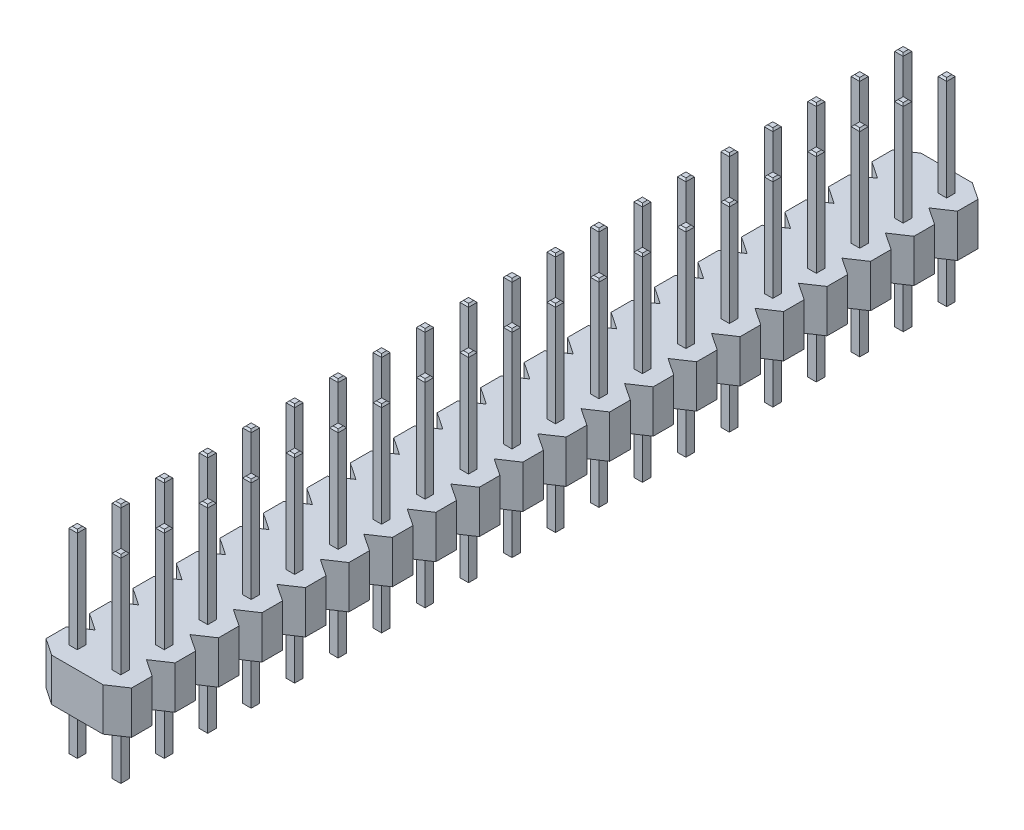
SolidWorks part; units mm, degrees
ref_plane "Front" through (0, 0, 0) normal (0, 0, 1) x (1, 0, 0)
ref_plane "Top" through (0, 0, 0) normal (0, 1, 0) x (1, 0, 0)
ref_plane "Right" through (0, 0, 0) normal (1, 0, 0) x (0, 0, -1)
ref_plane "Plan1" through (0, 2.5, 0) normal (0, 1, 0) x (1, 0, 0)
sketch "Esquisse1" plane through (0, 2.5, 0) normal (0, 1, 0) x (1, 0, 0)
  line L0 (2.5, -23.46) -> (2.5, 26)
  line L1 (2.5, 26) -> (1.5, 26.67)
  line L2 (1.5, 26.67) -> (-1.5, 26.67)
  line L3 (-1.5, 26.67) -> (-2.5, 26)
  line L4 (-2.5, 26) -> (-2.5, -23.46)
  line L5 (-2.5, -23.46) -> (-1.5, -24.13)
  line L6 (-1.5, -24.13) -> (1.5, -24.13)
  line L7 (1.5, -24.13) -> (2.5, -23.46)
extrude "Boss.-Extru.1" add sketch "Esquisse1" against normal blind 2.5
sketch "Esquisse2" plane through (0, 0, 0) normal (0, -1, 0) x (1, 0, 0)
  line L0 (-2.5, 7.02) -> (-2.5, 5.68)
  line L1 (-2.5, 5.68) -> (-1.5, 6.35)
  line L2 (-1.5, 6.35) -> (-2.5, 7.02)
extrude "Enlèv. mat.-Extru.1" cut sketch "Esquisse2" against normal through all
sketch "Esquisse3" plane through (0, 0, 0) normal (0, -1, 0) x (1, 0, 0)
  line L0 (-2.5, 9.56) -> (-2.5, 8.22)
  line L1 (-2.5, 8.22) -> (-1.5, 8.89)
  line L2 (-1.5, 8.89) -> (-2.5, 9.56)
extrude "Enlèv. mat.-Extru.2" cut sketch "Esquisse3" against normal through all
sketch "Esquisse4" plane through (0, 0, 0) normal (0, -1, 0) x (1, 0, 0)
  line L0 (-2.5, 12.1) -> (-2.5, 10.76)
  line L1 (-2.5, 10.76) -> (-1.5, 11.43)
  line L2 (-1.5, 11.43) -> (-2.5, 12.1)
extrude "Enlèv. mat.-Extru.3" cut sketch "Esquisse4" against normal through all
sketch "Esquisse5" plane through (0, 0, 0) normal (0, -1, 0) x (1, 0, 0)
  line L0 (-2.5, 14.64) -> (-2.5, 13.3)
  line L1 (-2.5, 13.3) -> (-1.5, 13.97)
  line L2 (-1.5, 13.97) -> (-2.5, 14.64)
extrude "Enlèv. mat.-Extru.4" cut sketch "Esquisse5" against normal through all
sketch "Esquisse6" plane through (0, 0, 0) normal (0, -1, 0) x (1, 0, 0)
  line L0 (-2.5, 17.18) -> (-2.5, 15.84)
  line L1 (-2.5, 15.84) -> (-1.5, 16.51)
  line L2 (-1.5, 16.51) -> (-2.5, 17.18)
extrude "Enlèv. mat.-Extru.5" cut sketch "Esquisse6" against normal through all
sketch "Esquisse7" plane through (0, 0, 0) normal (0, -1, 0) x (1, 0, 0)
  line L0 (-2.5, 19.72) -> (-2.5, 18.38)
  line L1 (-2.5, 18.38) -> (-1.5, 19.05)
  line L2 (-1.5, 19.05) -> (-2.5, 19.72)
extrude "Enlèv. mat.-Extru.6" cut sketch "Esquisse7" against normal through all
sketch "Esquisse8" plane through (0, 0, 0) normal (0, -1, 0) x (1, 0, 0)
  line L0 (-2.5, 22.26) -> (-2.5, 20.92)
  line L1 (-2.5, 20.92) -> (-1.5, 21.59)
  line L2 (-1.5, 21.59) -> (-2.5, 22.26)
extrude "Enlèv. mat.-Extru.7" cut sketch "Esquisse8" against normal through all
sketch "Esquisse9" plane through (0, 0, 0) normal (0, -1, 0) x (1, 0, 0)
  line L0 (2.5, 20.92) -> (2.5, 22.26)
  line L1 (2.5, 22.26) -> (1.5, 21.59)
  line L2 (1.5, 21.59) -> (2.5, 20.92)
extrude "Enlèv. mat.-Extru.8" cut sketch "Esquisse9" against normal through all
sketch "Esquisse10" plane through (0, 0, 0) normal (0, -1, 0) x (1, 0, 0)
  line L0 (2.5, 18.38) -> (2.5, 19.72)
  line L1 (2.5, 19.72) -> (1.5, 19.05)
  line L2 (1.5, 19.05) -> (2.5, 18.38)
extrude "Enlèv. mat.-Extru.9" cut sketch "Esquisse10" against normal through all
sketch "Esquisse11" plane through (0, 0, 0) normal (0, -1, 0) x (1, 0, 0)
  line L0 (2.5, 15.84) -> (2.5, 17.18)
  line L1 (2.5, 17.18) -> (1.5, 16.51)
  line L2 (1.5, 16.51) -> (2.5, 15.84)
extrude "Enlèv. mat.-Extru.10" cut sketch "Esquisse11" against normal through all
sketch "Esquisse12" plane through (0, 0, 0) normal (0, -1, 0) x (1, 0, 0)
  line L0 (2.5, 13.3) -> (2.5, 14.64)
  line L1 (2.5, 14.64) -> (1.5, 13.97)
  line L2 (1.5, 13.97) -> (2.5, 13.3)
extrude "Enlèv. mat.-Extru.11" cut sketch "Esquisse12" against normal through all
sketch "Esquisse13" plane through (0, 0, 0) normal (0, -1, 0) x (1, 0, 0)
  line L0 (2.5, 10.76) -> (2.5, 12.1)
  line L1 (2.5, 12.1) -> (1.5, 11.43)
  line L2 (1.5, 11.43) -> (2.5, 10.76)
extrude "Enlèv. mat.-Extru.12" cut sketch "Esquisse13" against normal through all
sketch "Esquisse14" plane through (0, 0, 0) normal (0, -1, 0) x (1, 0, 0)
  line L0 (2.5, 8.22) -> (2.5, 9.56)
  line L1 (2.5, 9.56) -> (1.5, 8.89)
  line L2 (1.5, 8.89) -> (2.5, 8.22)
extrude "Enlèv. mat.-Extru.13" cut sketch "Esquisse14" against normal through all
sketch "Esquisse15" plane through (0, 0, 0) normal (0, -1, 0) x (1, 0, 0)
  line L0 (2.5, 5.68) -> (2.5, 7.02)
  line L1 (2.5, 7.02) -> (1.5, 6.35)
  line L2 (1.5, 6.35) -> (2.5, 5.68)
extrude "Enlèv. mat.-Extru.14" cut sketch "Esquisse15" against normal through all
sketch "Esquisse16" plane through (0, 0, 0) normal (0, -1, 0) x (1, 0, 0)
  line L0 (2.5, 3.14) -> (2.5, 4.48)
  line L1 (2.5, 4.48) -> (1.5, 3.81)
  line L2 (1.5, 3.81) -> (2.5, 3.14)
extrude "Enlèv. mat.-Extru.15" cut sketch "Esquisse16" against normal through all
sketch "Esquisse17" plane through (0, 0, 0) normal (0, -1, 0) x (1, 0, 0)
  line L0 (2.5, 0.6) -> (2.5, 1.94)
  line L1 (2.5, 1.94) -> (1.5, 1.27)
  line L2 (1.5, 1.27) -> (2.5, 0.6)
extrude "Enlèv. mat.-Extru.16" cut sketch "Esquisse17" against normal through all
sketch "Esquisse18" plane through (0, 0, 0) normal (0, -1, 0) x (1, 0, 0)
  line L0 (2.5, -1.94) -> (2.5, -0.6)
  line L1 (2.5, -0.6) -> (1.5, -1.27)
  line L2 (1.5, -1.27) -> (2.5, -1.94)
extrude "Enlèv. mat.-Extru.17" cut sketch "Esquisse18" against normal through all
sketch "Esquisse19" plane through (0, 0, 0) normal (0, -1, 0) x (1, 0, 0)
  line L0 (2.5, -4.48) -> (2.5, -3.14)
  line L1 (2.5, -3.14) -> (1.5, -3.81)
  line L2 (1.5, -3.81) -> (2.5, -4.48)
extrude "Enlèv. mat.-Extru.18" cut sketch "Esquisse19" against normal through all
sketch "Esquisse20" plane through (0, 0, 0) normal (0, -1, 0) x (1, 0, 0)
  line L0 (2.5, -7.02) -> (2.5, -5.68)
  line L1 (2.5, -5.68) -> (1.5, -6.35)
  line L2 (1.5, -6.35) -> (2.5, -7.02)
extrude "Enlèv. mat.-Extru.19" cut sketch "Esquisse20" against normal through all
sketch "Esquisse21" plane through (0, 0, 0) normal (0, -1, 0) x (1, 0, 0)
  line L0 (2.5, -9.56) -> (2.5, -8.22)
  line L1 (2.5, -8.22) -> (1.5, -8.89)
  line L2 (1.5, -8.89) -> (2.5, -9.56)
extrude "Enlèv. mat.-Extru.20" cut sketch "Esquisse21" against normal through all
sketch "Esquisse22" plane through (0, 0, 0) normal (0, -1, 0) x (1, 0, 0)
  line L0 (2.5, -12.1) -> (2.5, -10.76)
  line L1 (2.5, -10.76) -> (1.5, -11.43)
  line L2 (1.5, -11.43) -> (2.5, -12.1)
extrude "Enlèv. mat.-Extru.21" cut sketch "Esquisse22" against normal through all
sketch "Esquisse23" plane through (0, 0, 0) normal (0, -1, 0) x (1, 0, 0)
  line L0 (2.5, -14.64) -> (2.5, -13.3)
  line L1 (2.5, -13.3) -> (1.5, -13.97)
  line L2 (1.5, -13.97) -> (2.5, -14.64)
extrude "Enlèv. mat.-Extru.22" cut sketch "Esquisse23" against normal through all
sketch "Esquisse24" plane through (0, 0, 0) normal (0, -1, 0) x (1, 0, 0)
  line L0 (2.5, -17.18) -> (2.5, -15.84)
  line L1 (2.5, -15.84) -> (1.5, -16.51)
  line L2 (1.5, -16.51) -> (2.5, -17.18)
extrude "Enlèv. mat.-Extru.23" cut sketch "Esquisse24" against normal through all
sketch "Esquisse25" plane through (0, 0, 0) normal (0, -1, 0) x (1, 0, 0)
  line L0 (2.5, -19.72) -> (2.5, -18.38)
  line L1 (2.5, -18.38) -> (1.5, -19.05)
  line L2 (1.5, -19.05) -> (2.5, -19.72)
extrude "Enlèv. mat.-Extru.24" cut sketch "Esquisse25" against normal through all
sketch "Esquisse26" plane through (0, 0, 0) normal (0, -1, 0) x (1, 0, 0)
  line L0 (2.5, -22.26) -> (2.5, -20.92)
  line L1 (2.5, -20.92) -> (1.5, -21.59)
  line L2 (1.5, -21.59) -> (2.5, -22.26)
extrude "Enlèv. mat.-Extru.25" cut sketch "Esquisse26" against normal through all
sketch "Esquisse27" plane through (0, 0, 0) normal (0, -1, 0) x (1, 0, 0)
  line L0 (2.5, -24.8) -> (2.5, -23.46)
  line L1 (2.5, -23.46) -> (1.5, -24.13)
  line L2 (1.5, -24.13) -> (2.5, -24.8)
extrude "Enlèv. mat.-Extru.26" cut sketch "Esquisse27" against normal through all
sketch "Esquisse28" plane through (0, 0, 0) normal (0, -1, 0) x (1, 0, 0)
  line L0 (-2.5, -23.46) -> (-2.5, -24.8)
  line L1 (-2.5, -24.8) -> (-1.5, -24.13)
  line L2 (-1.5, -24.13) -> (-2.5, -23.46)
extrude "Enlèv. mat.-Extru.27" cut sketch "Esquisse28" against normal through all
sketch "Esquisse29" plane through (0, 0, 0) normal (0, -1, 0) x (1, 0, 0)
  line L0 (-2.5, -20.92) -> (-2.5, -22.26)
  line L1 (-2.5, -22.26) -> (-1.5, -21.59)
  line L2 (-1.5, -21.59) -> (-2.5, -20.92)
extrude "Enlèv. mat.-Extru.28" cut sketch "Esquisse29" against normal through all
sketch "Esquisse30" plane through (0, 0, 0) normal (0, -1, 0) x (1, 0, 0)
  line L0 (-2.5, -18.38) -> (-2.5, -19.72)
  line L1 (-2.5, -19.72) -> (-1.5, -19.05)
  line L2 (-1.5, -19.05) -> (-2.5, -18.38)
extrude "Enlèv. mat.-Extru.29" cut sketch "Esquisse30" against normal through all
sketch "Esquisse31" plane through (0, 0, 0) normal (0, -1, 0) x (1, 0, 0)
  line L0 (-2.5, -15.84) -> (-2.5, -17.18)
  line L1 (-2.5, -17.18) -> (-1.5, -16.51)
  line L2 (-1.5, -16.51) -> (-2.5, -15.84)
extrude "Enlèv. mat.-Extru.30" cut sketch "Esquisse31" against normal through all
sketch "Esquisse32" plane through (0, 0, 0) normal (0, -1, 0) x (1, 0, 0)
  line L0 (-2.5, -13.3) -> (-2.5, -14.64)
  line L1 (-2.5, -14.64) -> (-1.5, -13.97)
  line L2 (-1.5, -13.97) -> (-2.5, -13.3)
extrude "Enlèv. mat.-Extru.31" cut sketch "Esquisse32" against normal through all
sketch "Esquisse33" plane through (0, 0, 0) normal (0, -1, 0) x (1, 0, 0)
  line L0 (-2.5, -10.76) -> (-2.5, -12.1)
  line L1 (-2.5, -12.1) -> (-1.5, -11.43)
  line L2 (-1.5, -11.43) -> (-2.5, -10.76)
extrude "Enlèv. mat.-Extru.32" cut sketch "Esquisse33" against normal through all
sketch "Esquisse34" plane through (0, 0, 0) normal (0, -1, 0) x (1, 0, 0)
  line L0 (-2.5, -8.22) -> (-2.5, -9.56)
  line L1 (-2.5, -9.56) -> (-1.5, -8.89)
  line L2 (-1.5, -8.89) -> (-2.5, -8.22)
extrude "Enlèv. mat.-Extru.33" cut sketch "Esquisse34" against normal through all
sketch "Esquisse35" plane through (0, 0, 0) normal (0, -1, 0) x (1, 0, 0)
  line L0 (-2.5, -5.68) -> (-2.5, -7.02)
  line L1 (-2.5, -7.02) -> (-1.5, -6.35)
  line L2 (-1.5, -6.35) -> (-2.5, -5.68)
extrude "Enlèv. mat.-Extru.34" cut sketch "Esquisse35" against normal through all
sketch "Esquisse36" plane through (0, 0, 0) normal (0, -1, 0) x (1, 0, 0)
  line L0 (-2.5, -3.14) -> (-2.5, -4.48)
  line L1 (-2.5, -4.48) -> (-1.5, -3.81)
  line L2 (-1.5, -3.81) -> (-2.5, -3.14)
extrude "Enlèv. mat.-Extru.35" cut sketch "Esquisse36" against normal through all
sketch "Esquisse37" plane through (0, 0, 0) normal (0, -1, 0) x (1, 0, 0)
  line L0 (-2.5, -0.6) -> (-2.5, -1.94)
  line L1 (-2.5, -1.94) -> (-1.5, -1.27)
  line L2 (-1.5, -1.27) -> (-2.5, -0.6)
extrude "Enlèv. mat.-Extru.36" cut sketch "Esquisse37" against normal through all
sketch "Esquisse38" plane through (0, 0, 0) normal (0, -1, 0) x (1, 0, 0)
  line L0 (-2.5, 1.94) -> (-2.5, 0.6)
  line L1 (-2.5, 0.6) -> (-1.5, 1.27)
  line L2 (-1.5, 1.27) -> (-2.5, 1.94)
extrude "Enlèv. mat.-Extru.37" cut sketch "Esquisse38" against normal through all
sketch "Esquisse39" plane through (0, 0, 0) normal (0, -1, 0) x (1, 0, 0)
  line L0 (-2.5, 4.48) -> (-2.5, 3.14)
  line L1 (-2.5, 3.14) -> (-1.5, 3.81)
  line L2 (-1.5, 3.81) -> (-2.5, 4.48)
extrude "Enlèv. mat.-Extru.38" cut sketch "Esquisse39" against normal through all
sketch "Esquisse40" plane through (0, 2.5, 0) normal (0, 1, 0) x (-1, 0, 0)
  line L0 (1.02, -2.29) -> (1.52, -2.29)
  line L1 (1.52, -2.29) -> (1.52, -2.79)
  line L2 (1.52, -2.79) -> (1.02, -2.79)
  line L3 (1.02, -2.79) -> (1.02, -2.29)
extrude "Boss.-Extru.2" add sketch "Esquisse40" along normal blind 6
sketch "Esquisse41" plane through (0, 2.5, 0) normal (0, 1, 0) x (-1, 0, 0)
  line L0 (-1.52, -2.79) -> (-1.52, -2.29)
  line L1 (-1.52, -2.29) -> (-1.02, -2.29)
  line L2 (-1.02, -2.29) -> (-1.02, -2.79)
  line L3 (-1.02, -2.79) -> (-1.52, -2.79)
extrude "Boss.-Extru.3" add sketch "Esquisse41" along normal blind 6
sketch "Esquisse42" plane through (0, 2.5, 0) normal (0, 1, 0) x (-1, 0, 0)
  line L0 (-1.52, -5.33) -> (-1.52, -4.83)
  line L1 (-1.52, -4.83) -> (-1.02, -4.83)
  line L2 (-1.02, -4.83) -> (-1.02, -5.33)
  line L3 (-1.02, -5.33) -> (-1.52, -5.33)
extrude "Boss.-Extru.4" add sketch "Esquisse42" along normal blind 6
sketch "Esquisse43" plane through (0, 2.5, 0) normal (0, 1, 0) x (-1, 0, 0)
  line L0 (1.02, -5.33) -> (1.02, -4.83)
  line L1 (1.02, -4.83) -> (1.52, -4.83)
  line L2 (1.52, -4.83) -> (1.52, -5.33)
  line L3 (1.52, -5.33) -> (1.02, -5.33)
extrude "Boss.-Extru.5" add sketch "Esquisse43" along normal blind 6
sketch "Esquisse44" plane through (0, 2.5, 0) normal (0, 1, 0) x (-1, 0, 0)
  line L0 (-1.52, -7.87) -> (-1.52, -7.37)
  line L1 (-1.52, -7.37) -> (-1.02, -7.37)
  line L2 (-1.02, -7.37) -> (-1.02, -7.87)
  line L3 (-1.02, -7.87) -> (-1.52, -7.87)
extrude "Boss.-Extru.6" add sketch "Esquisse44" along normal blind 6
sketch "Esquisse45" plane through (0, 2.5, 0) normal (0, 1, 0) x (-1, 0, 0)
  line L0 (1.02, -7.87) -> (1.02, -7.37)
  line L1 (1.02, -7.37) -> (1.52, -7.37)
  line L2 (1.52, -7.37) -> (1.52, -7.87)
  line L3 (1.52, -7.87) -> (1.02, -7.87)
extrude "Boss.-Extru.7" add sketch "Esquisse45" along normal blind 6
sketch "Esquisse46" plane through (0, 2.5, 0) normal (0, 1, 0) x (-1, 0, 0)
  line L0 (-1.52, -10.41) -> (-1.52, -9.91)
  line L1 (-1.52, -9.91) -> (-1.02, -9.91)
  line L2 (-1.02, -9.91) -> (-1.02, -10.41)
  line L3 (-1.02, -10.41) -> (-1.52, -10.41)
extrude "Boss.-Extru.8" add sketch "Esquisse46" along normal blind 6
sketch "Esquisse47" plane through (0, 2.5, 0) normal (0, 1, 0) x (-1, 0, 0)
  line L0 (1.52, -9.91) -> (1.52, -10.41)
  line L1 (1.52, -10.41) -> (1.02, -10.41)
  line L2 (1.02, -10.41) -> (1.02, -9.91)
  line L3 (1.02, -9.91) -> (1.52, -9.91)
extrude "Boss.-Extru.9" add sketch "Esquisse47" along normal blind 6
sketch "Esquisse48" plane through (0, 2.5, 0) normal (0, 1, 0) x (-1, 0, 0)
  line L0 (-1.52, -12.95) -> (-1.52, -12.45)
  line L1 (-1.52, -12.45) -> (-1.02, -12.45)
  line L2 (-1.02, -12.45) -> (-1.02, -12.95)
  line L3 (-1.02, -12.95) -> (-1.52, -12.95)
extrude "Boss.-Extru.10" add sketch "Esquisse48" along normal blind 6
sketch "Esquisse49" plane through (0, 2.5, 0) normal (0, 1, 0) x (-1, 0, 0)
  line L0 (1.02, -12.95) -> (1.02, -12.45)
  line L1 (1.02, -12.45) -> (1.52, -12.45)
  line L2 (1.52, -12.45) -> (1.52, -12.95)
  line L3 (1.52, -12.95) -> (1.02, -12.95)
extrude "Boss.-Extru.11" add sketch "Esquisse49" along normal blind 6
sketch "Esquisse50" plane through (0, 2.5, 0) normal (0, 1, 0) x (-1, 0, 0)
  line L0 (-1.52, -15.49) -> (-1.52, -14.99)
  line L1 (-1.52, -14.99) -> (-1.02, -14.99)
  line L2 (-1.02, -14.99) -> (-1.02, -15.49)
  line L3 (-1.02, -15.49) -> (-1.52, -15.49)
extrude "Boss.-Extru.12" add sketch "Esquisse50" along normal blind 6
sketch "Esquisse51" plane through (0, 2.5, 0) normal (0, 1, 0) x (-1, 0, 0)
  line L0 (1.02, -15.49) -> (1.02, -14.99)
  line L1 (1.02, -14.99) -> (1.52, -14.99)
  line L2 (1.52, -14.99) -> (1.52, -15.49)
  line L3 (1.52, -15.49) -> (1.02, -15.49)
extrude "Boss.-Extru.13" add sketch "Esquisse51" along normal blind 6
sketch "Esquisse52" plane through (0, 2.5, 0) normal (0, 1, 0) x (-1, 0, 0)
  line L0 (-1.52, -18.03) -> (-1.52, -17.53)
  line L1 (-1.52, -17.53) -> (-1.02, -17.53)
  line L2 (-1.02, -17.53) -> (-1.02, -18.03)
  line L3 (-1.02, -18.03) -> (-1.52, -18.03)
extrude "Boss.-Extru.14" add sketch "Esquisse52" along normal blind 6
sketch "Esquisse53" plane through (0, 2.5, 0) normal (0, 1, 0) x (-1, 0, 0)
  line L0 (1.02, -18.03) -> (1.02, -17.53)
  line L1 (1.02, -17.53) -> (1.52, -17.53)
  line L2 (1.52, -17.53) -> (1.52, -18.03)
  line L3 (1.52, -18.03) -> (1.02, -18.03)
extrude "Boss.-Extru.15" add sketch "Esquisse53" along normal blind 6
sketch "Esquisse54" plane through (0, 2.5, 0) normal (0, 1, 0) x (-1, 0, 0)
  line L0 (-1.52, -20.57) -> (-1.52, -20.07)
  line L1 (-1.52, -20.07) -> (-1.02, -20.07)
  line L2 (-1.02, -20.07) -> (-1.02, -20.57)
  line L3 (-1.02, -20.57) -> (-1.52, -20.57)
extrude "Boss.-Extru.16" add sketch "Esquisse54" along normal blind 6
sketch "Esquisse55" plane through (0, 2.5, 0) normal (0, 1, 0) x (-1, 0, 0)
  line L0 (1.52, -20.07) -> (1.52, -20.57)
  line L1 (1.52, -20.57) -> (1.02, -20.57)
  line L2 (1.02, -20.57) -> (1.02, -20.07)
  line L3 (1.02, -20.07) -> (1.52, -20.07)
extrude "Boss.-Extru.17" add sketch "Esquisse55" along normal blind 6
sketch "Esquisse56" plane through (0, 2.5, 0) normal (0, 1, 0) x (-1, 0, 0)
  line L0 (-1.52, -23.11) -> (-1.52, -22.61)
  line L1 (-1.52, -22.61) -> (-1.02, -22.61)
  line L2 (-1.02, -22.61) -> (-1.02, -23.11)
  line L3 (-1.02, -23.11) -> (-1.52, -23.11)
extrude "Boss.-Extru.18" add sketch "Esquisse56" along normal blind 6
sketch "Esquisse57" plane through (0, 2.5, 0) normal (0, 1, 0) x (-1, 0, 0)
  line L0 (1.02, -23.11) -> (1.02, -22.61)
  line L1 (1.02, -22.61) -> (1.52, -22.61)
  line L2 (1.52, -22.61) -> (1.52, -23.11)
  line L3 (1.52, -23.11) -> (1.02, -23.11)
extrude "Boss.-Extru.19" add sketch "Esquisse57" along normal blind 6
sketch "Esquisse58" plane through (0, 2.5, 0) normal (0, 1, 0) x (-1, 0, 0)
  line L0 (-1.52, -25.65) -> (-1.52, -25.15)
  line L1 (-1.52, -25.15) -> (-1.02, -25.15)
  line L2 (-1.02, -25.15) -> (-1.02, -25.65)
  line L3 (-1.02, -25.65) -> (-1.52, -25.65)
extrude "Boss.-Extru.20" add sketch "Esquisse58" along normal blind 6
sketch "Esquisse59" plane through (0, 2.5, 0) normal (0, 1, 0) x (-1, 0, 0)
  line L0 (1.52, -25.15) -> (1.52, -25.65)
  line L1 (1.52, -25.65) -> (1.02, -25.65)
  line L2 (1.02, -25.65) -> (1.02, -25.15)
  line L3 (1.02, -25.15) -> (1.52, -25.15)
extrude "Boss.-Extru.21" add sketch "Esquisse59" along normal blind 6
sketch "Esquisse60" plane through (0, 2.5, 0) normal (0, 1, 0) x (-1, 0, 0)
  line L0 (1.52, 22.61) -> (1.02, 22.61)
  line L1 (1.02, 22.61) -> (1.02, 23.11)
  line L2 (1.02, 23.11) -> (1.52, 23.11)
  line L3 (1.52, 23.11) -> (1.52, 22.61)
extrude "Boss.-Extru.22" add sketch "Esquisse60" along normal blind 6
sketch "Esquisse61" plane through (0, 2.5, 0) normal (0, 1, 0) x (-1, 0, 0)
  line L0 (-1.02, 22.61) -> (-1.52, 22.61)
  line L1 (-1.52, 22.61) -> (-1.52, 23.11)
  line L2 (-1.52, 23.11) -> (-1.02, 23.11)
  line L3 (-1.02, 23.11) -> (-1.02, 22.61)
extrude "Boss.-Extru.23" add sketch "Esquisse61" along normal blind 6
sketch "Esquisse62" plane through (0, 2.5, 0) normal (0, 1, 0) x (-1, 0, 0)
  line L0 (-1.02, 20.07) -> (-1.52, 20.07)
  line L1 (-1.52, 20.07) -> (-1.52, 20.57)
  line L2 (-1.52, 20.57) -> (-1.02, 20.57)
  line L3 (-1.02, 20.57) -> (-1.02, 20.07)
extrude "Boss.-Extru.24" add sketch "Esquisse62" along normal blind 6
sketch "Esquisse63" plane through (0, 2.5, 0) normal (0, 1, 0) x (-1, 0, 0)
  line L0 (1.52, 20.57) -> (1.52, 20.07)
  line L1 (1.52, 20.07) -> (1.02, 20.07)
  line L2 (1.02, 20.07) -> (1.02, 20.57)
  line L3 (1.02, 20.57) -> (1.52, 20.57)
extrude "Boss.-Extru.25" add sketch "Esquisse63" along normal blind 6
sketch "Esquisse64" plane through (0, 2.5, 0) normal (0, 1, 0) x (-1, 0, 0)
  line L0 (-1.02, 17.53) -> (-1.52, 17.53)
  line L1 (-1.52, 17.53) -> (-1.52, 18.03)
  line L2 (-1.52, 18.03) -> (-1.02, 18.03)
  line L3 (-1.02, 18.03) -> (-1.02, 17.53)
extrude "Boss.-Extru.26" add sketch "Esquisse64" along normal blind 6
sketch "Esquisse65" plane through (0, 2.5, 0) normal (0, 1, 0) x (-1, 0, 0)
  line L0 (1.52, 17.53) -> (1.02, 17.53)
  line L1 (1.02, 17.53) -> (1.02, 18.03)
  line L2 (1.02, 18.03) -> (1.52, 18.03)
  line L3 (1.52, 18.03) -> (1.52, 17.53)
extrude "Boss.-Extru.27" add sketch "Esquisse65" along normal blind 6
sketch "Esquisse66" plane through (0, 2.5, 0) normal (0, 1, 0) x (-1, 0, 0)
  line L0 (-1.02, 14.99) -> (-1.52, 14.99)
  line L1 (-1.52, 14.99) -> (-1.52, 15.49)
  line L2 (-1.52, 15.49) -> (-1.02, 15.49)
  line L3 (-1.02, 15.49) -> (-1.02, 14.99)
extrude "Boss.-Extru.28" add sketch "Esquisse66" along normal blind 6
sketch "Esquisse67" plane through (0, 2.5, 0) normal (0, 1, 0) x (-1, 0, 0)
  line L0 (1.52, 14.99) -> (1.02, 14.99)
  line L1 (1.02, 14.99) -> (1.02, 15.49)
  line L2 (1.02, 15.49) -> (1.52, 15.49)
  line L3 (1.52, 15.49) -> (1.52, 14.99)
extrude "Boss.-Extru.29" add sketch "Esquisse67" along normal blind 6
sketch "Esquisse68" plane through (0, 2.5, 0) normal (0, 1, 0) x (-1, 0, 0)
  line L0 (-1.02, 12.45) -> (-1.52, 12.45)
  line L1 (-1.52, 12.45) -> (-1.52, 12.95)
  line L2 (-1.52, 12.95) -> (-1.02, 12.95)
  line L3 (-1.02, 12.95) -> (-1.02, 12.45)
extrude "Boss.-Extru.30" add sketch "Esquisse68" along normal blind 6
sketch "Esquisse69" plane through (0, 2.5, 0) normal (0, 1, 0) x (-1, 0, 0)
  line L0 (1.52, 12.45) -> (1.02, 12.45)
  line L1 (1.02, 12.45) -> (1.02, 12.95)
  line L2 (1.02, 12.95) -> (1.52, 12.95)
  line L3 (1.52, 12.95) -> (1.52, 12.45)
extrude "Boss.-Extru.31" add sketch "Esquisse69" along normal blind 6
sketch "Esquisse70" plane through (0, 2.5, 0) normal (0, 1, 0) x (-1, 0, 0)
  line L0 (-1.02, 9.91) -> (-1.52, 9.91)
  line L1 (-1.52, 9.91) -> (-1.52, 10.41)
  line L2 (-1.52, 10.41) -> (-1.02, 10.41)
  line L3 (-1.02, 10.41) -> (-1.02, 9.91)
extrude "Boss.-Extru.32" add sketch "Esquisse70" along normal blind 6
sketch "Esquisse71" plane through (0, 2.5, 0) normal (0, 1, 0) x (-1, 0, 0)
  line L0 (1.52, 9.91) -> (1.02, 9.91)
  line L1 (1.02, 9.91) -> (1.02, 10.41)
  line L2 (1.02, 10.41) -> (1.52, 10.41)
  line L3 (1.52, 10.41) -> (1.52, 9.91)
extrude "Boss.-Extru.33" add sketch "Esquisse71" along normal blind 6
sketch "Esquisse72" plane through (0, 2.5, 0) normal (0, 1, 0) x (-1, 0, 0)
  line L0 (-1.02, 7.37) -> (-1.52, 7.37)
  line L1 (-1.52, 7.37) -> (-1.52, 7.87)
  line L2 (-1.52, 7.87) -> (-1.02, 7.87)
  line L3 (-1.02, 7.87) -> (-1.02, 7.37)
extrude "Boss.-Extru.34" add sketch "Esquisse72" along normal blind 6
sketch "Esquisse73" plane through (0, 2.5, 0) normal (0, 1, 0) x (-1, 0, 0)
  line L0 (1.52, 7.37) -> (1.02, 7.37)
  line L1 (1.02, 7.37) -> (1.02, 7.87)
  line L2 (1.02, 7.87) -> (1.52, 7.87)
  line L3 (1.52, 7.87) -> (1.52, 7.37)
extrude "Boss.-Extru.35" add sketch "Esquisse73" along normal blind 6
sketch "Esquisse74" plane through (0, 2.5, 0) normal (0, 1, 0) x (-1, 0, 0)
  line L0 (-1.02, 4.83) -> (-1.52, 4.83)
  line L1 (-1.52, 4.83) -> (-1.52, 5.33)
  line L2 (-1.52, 5.33) -> (-1.02, 5.33)
  line L3 (-1.02, 5.33) -> (-1.02, 4.83)
extrude "Boss.-Extru.36" add sketch "Esquisse74" along normal blind 6
sketch "Esquisse75" plane through (0, 2.5, 0) normal (0, 1, 0) x (-1, 0, 0)
  line L0 (1.52, 4.83) -> (1.02, 4.83)
  line L1 (1.02, 4.83) -> (1.02, 5.33)
  line L2 (1.02, 5.33) -> (1.52, 5.33)
  line L3 (1.52, 5.33) -> (1.52, 4.83)
extrude "Boss.-Extru.37" add sketch "Esquisse75" along normal blind 6
sketch "Esquisse76" plane through (0, 2.5, 0) normal (0, 1, 0) x (-1, 0, 0)
  line L0 (-1.02, 2.29) -> (-1.52, 2.29)
  line L1 (-1.52, 2.29) -> (-1.52, 2.79)
  line L2 (-1.52, 2.79) -> (-1.02, 2.79)
  line L3 (-1.02, 2.79) -> (-1.02, 2.29)
extrude "Boss.-Extru.38" add sketch "Esquisse76" along normal blind 6
sketch "Esquisse77" plane through (0, 2.5, 0) normal (0, 1, 0) x (-1, 0, 0)
  line L0 (1.52, 2.29) -> (1.02, 2.29)
  line L1 (1.02, 2.29) -> (1.02, 2.79)
  line L2 (1.02, 2.79) -> (1.52, 2.79)
  line L3 (1.52, 2.79) -> (1.52, 2.29)
extrude "Boss.-Extru.39" add sketch "Esquisse77" along normal blind 6
sketch "Esquisse78" plane through (0, 2.5, 0) normal (0, 1, 0) x (-1, 0, 0)
  line L0 (-1.02, -0.25) -> (-1.52, -0.25)
  line L1 (-1.52, -0.25) -> (-1.52, 0.25)
  line L2 (-1.52, 0.25) -> (-1.02, 0.25)
  line L3 (-1.02, 0.25) -> (-1.02, -0.25)
extrude "Boss.-Extru.40" add sketch "Esquisse78" along normal blind 6
sketch "Esquisse79" plane through (0, 2.5, 0) normal (0, 1, 0) x (-1, 0, 0)
  line L0 (1.52, 0.25) -> (1.52, -0.25)
  line L1 (1.52, -0.25) -> (1.02, -0.25)
  line L2 (1.02, -0.25) -> (1.02, 0.25)
  line L3 (1.02, 0.25) -> (1.52, 0.25)
extrude "Boss.-Extru.41" add sketch "Esquisse79" along normal blind 6
sketch "Esquisse80" plane through (0, 0, 0) normal (0, -1, 0) x (1, 0, 0)
  line L0 (-1.02, -2.29) -> (-1.02, -2.79)
  line L1 (-1.02, -2.79) -> (-1.52, -2.79)
  line L2 (-1.52, -2.79) -> (-1.52, -2.29)
  line L3 (-1.52, -2.29) -> (-1.02, -2.29)
extrude "Boss.-Extru.42" add sketch "Esquisse80" along normal blind 3
sketch "Esquisse81" plane through (0, 0, 0) normal (0, -1, 0) x (1, 0, 0)
  line L0 (1.52, -2.29) -> (1.52, -2.79)
  line L1 (1.52, -2.79) -> (1.02, -2.79)
  line L2 (1.02, -2.79) -> (1.02, -2.29)
  line L3 (1.02, -2.29) -> (1.52, -2.29)
extrude "Boss.-Extru.43" add sketch "Esquisse81" along normal blind 3
sketch "Esquisse82" plane through (0, 0, 0) normal (0, -1, 0) x (1, 0, 0)
  line L0 (1.52, -4.83) -> (1.52, -5.33)
  line L1 (1.52, -5.33) -> (1.02, -5.33)
  line L2 (1.02, -5.33) -> (1.02, -4.83)
  line L3 (1.02, -4.83) -> (1.52, -4.83)
extrude "Boss.-Extru.44" add sketch "Esquisse82" along normal blind 3
sketch "Esquisse83" plane through (0, 0, 0) normal (0, -1, 0) x (1, 0, 0)
  line L0 (-1.02, -4.83) -> (-1.02, -5.33)
  line L1 (-1.02, -5.33) -> (-1.52, -5.33)
  line L2 (-1.52, -5.33) -> (-1.52, -4.83)
  line L3 (-1.52, -4.83) -> (-1.02, -4.83)
extrude "Boss.-Extru.45" add sketch "Esquisse83" along normal blind 3
sketch "Esquisse84" plane through (0, 0, 0) normal (0, -1, 0) x (1, 0, 0)
  line L0 (1.52, -7.37) -> (1.52, -7.87)
  line L1 (1.52, -7.87) -> (1.02, -7.87)
  line L2 (1.02, -7.87) -> (1.02, -7.37)
  line L3 (1.02, -7.37) -> (1.52, -7.37)
extrude "Boss.-Extru.46" add sketch "Esquisse84" along normal blind 3
sketch "Esquisse85" plane through (0, 0, 0) normal (0, -1, 0) x (1, 0, 0)
  line L0 (-1.02, -7.37) -> (-1.02, -7.87)
  line L1 (-1.02, -7.87) -> (-1.52, -7.87)
  line L2 (-1.52, -7.87) -> (-1.52, -7.37)
  line L3 (-1.52, -7.37) -> (-1.02, -7.37)
extrude "Boss.-Extru.47" add sketch "Esquisse85" along normal blind 3
sketch "Esquisse86" plane through (0, 0, 0) normal (0, -1, 0) x (1, 0, 0)
  line L0 (1.52, -9.91) -> (1.52, -10.41)
  line L1 (1.52, -10.41) -> (1.02, -10.41)
  line L2 (1.02, -10.41) -> (1.02, -9.91)
  line L3 (1.02, -9.91) -> (1.52, -9.91)
extrude "Boss.-Extru.48" add sketch "Esquisse86" along normal blind 3
sketch "Esquisse87" plane through (0, 0, 0) normal (0, -1, 0) x (1, 0, 0)
  line L0 (-1.02, -9.91) -> (-1.02, -10.41)
  line L1 (-1.02, -10.41) -> (-1.52, -10.41)
  line L2 (-1.52, -10.41) -> (-1.52, -9.91)
  line L3 (-1.52, -9.91) -> (-1.02, -9.91)
extrude "Boss.-Extru.49" add sketch "Esquisse87" along normal blind 3
sketch "Esquisse88" plane through (0, 0, 0) normal (0, -1, 0) x (1, 0, 0)
  line L0 (1.52, -12.45) -> (1.52, -12.95)
  line L1 (1.52, -12.95) -> (1.02, -12.95)
  line L2 (1.02, -12.95) -> (1.02, -12.45)
  line L3 (1.02, -12.45) -> (1.52, -12.45)
extrude "Boss.-Extru.50" add sketch "Esquisse88" along normal blind 3
sketch "Esquisse89" plane through (0, 0, 0) normal (0, -1, 0) x (1, 0, 0)
  line L0 (-1.02, -12.45) -> (-1.02, -12.95)
  line L1 (-1.02, -12.95) -> (-1.52, -12.95)
  line L2 (-1.52, -12.95) -> (-1.52, -12.45)
  line L3 (-1.52, -12.45) -> (-1.02, -12.45)
extrude "Boss.-Extru.51" add sketch "Esquisse89" along normal blind 3
sketch "Esquisse90" plane through (0, 0, 0) normal (0, -1, 0) x (1, 0, 0)
  line L0 (1.52, -14.99) -> (1.52, -15.49)
  line L1 (1.52, -15.49) -> (1.02, -15.49)
  line L2 (1.02, -15.49) -> (1.02, -14.99)
  line L3 (1.02, -14.99) -> (1.52, -14.99)
extrude "Boss.-Extru.52" add sketch "Esquisse90" along normal blind 3
sketch "Esquisse91" plane through (0, 0, 0) normal (0, -1, 0) x (1, 0, 0)
  line L0 (-1.02, -14.99) -> (-1.02, -15.49)
  line L1 (-1.02, -15.49) -> (-1.52, -15.49)
  line L2 (-1.52, -15.49) -> (-1.52, -14.99)
  line L3 (-1.52, -14.99) -> (-1.02, -14.99)
extrude "Boss.-Extru.53" add sketch "Esquisse91" along normal blind 3
sketch "Esquisse92" plane through (0, 0, 0) normal (0, -1, 0) x (1, 0, 0)
  line L0 (1.52, -17.53) -> (1.52, -18.03)
  line L1 (1.52, -18.03) -> (1.02, -18.03)
  line L2 (1.02, -18.03) -> (1.02, -17.53)
  line L3 (1.02, -17.53) -> (1.52, -17.53)
extrude "Boss.-Extru.54" add sketch "Esquisse92" along normal blind 3
sketch "Esquisse93" plane through (0, 0, 0) normal (0, -1, 0) x (1, 0, 0)
  line L0 (-1.02, -17.53) -> (-1.02, -18.03)
  line L1 (-1.02, -18.03) -> (-1.52, -18.03)
  line L2 (-1.52, -18.03) -> (-1.52, -17.53)
  line L3 (-1.52, -17.53) -> (-1.02, -17.53)
extrude "Boss.-Extru.55" add sketch "Esquisse93" along normal blind 3
sketch "Esquisse94" plane through (0, 0, 0) normal (0, -1, 0) x (1, 0, 0)
  line L0 (1.52, -20.07) -> (1.52, -20.57)
  line L1 (1.52, -20.57) -> (1.02, -20.57)
  line L2 (1.02, -20.57) -> (1.02, -20.07)
  line L3 (1.02, -20.07) -> (1.52, -20.07)
extrude "Boss.-Extru.56" add sketch "Esquisse94" along normal blind 3
sketch "Esquisse95" plane through (0, 0, 0) normal (0, -1, 0) x (1, 0, 0)
  line L0 (-1.02, -20.07) -> (-1.02, -20.57)
  line L1 (-1.02, -20.57) -> (-1.52, -20.57)
  line L2 (-1.52, -20.57) -> (-1.52, -20.07)
  line L3 (-1.52, -20.07) -> (-1.02, -20.07)
extrude "Boss.-Extru.57" add sketch "Esquisse95" along normal blind 3
sketch "Esquisse96" plane through (0, 0, 0) normal (0, -1, 0) x (1, 0, 0)
  line L0 (1.52, -22.61) -> (1.52, -23.11)
  line L1 (1.52, -23.11) -> (1.02, -23.11)
  line L2 (1.02, -23.11) -> (1.02, -22.61)
  line L3 (1.02, -22.61) -> (1.52, -22.61)
extrude "Boss.-Extru.58" add sketch "Esquisse96" along normal blind 3
sketch "Esquisse97" plane through (0, 0, 0) normal (0, -1, 0) x (1, 0, 0)
  line L0 (-1.02, -22.61) -> (-1.02, -23.11)
  line L1 (-1.02, -23.11) -> (-1.52, -23.11)
  line L2 (-1.52, -23.11) -> (-1.52, -22.61)
  line L3 (-1.52, -22.61) -> (-1.02, -22.61)
extrude "Boss.-Extru.59" add sketch "Esquisse97" along normal blind 3
sketch "Esquisse98" plane through (0, 0, 0) normal (0, -1, 0) x (1, 0, 0)
  line L0 (1.52, -25.15) -> (1.52, -25.65)
  line L1 (1.52, -25.65) -> (1.02, -25.65)
  line L2 (1.02, -25.65) -> (1.02, -25.15)
  line L3 (1.02, -25.15) -> (1.52, -25.15)
extrude "Boss.-Extru.60" add sketch "Esquisse98" along normal blind 3
sketch "Esquisse99" plane through (0, 0, 0) normal (0, -1, 0) x (1, 0, 0)
  line L0 (-1.02, -25.15) -> (-1.02, -25.65)
  line L1 (-1.02, -25.65) -> (-1.52, -25.65)
  line L2 (-1.52, -25.65) -> (-1.52, -25.15)
  line L3 (-1.52, -25.15) -> (-1.02, -25.15)
extrude "Boss.-Extru.61" add sketch "Esquisse99" along normal blind 3
sketch "Esquisse100" plane through (0, 0, 0) normal (0, -1, 0) x (1, 0, 0)
  line L0 (-1.02, 23.11) -> (-1.02, 22.61)
  line L1 (-1.02, 22.61) -> (-1.52, 22.61)
  line L2 (-1.52, 22.61) -> (-1.52, 23.11)
  line L3 (-1.52, 23.11) -> (-1.02, 23.11)
extrude "Boss.-Extru.62" add sketch "Esquisse100" along normal blind 3
sketch "Esquisse101" plane through (0, 0, 0) normal (0, -1, 0) x (1, 0, 0)
  line L0 (1.52, 23.11) -> (1.52, 22.61)
  line L1 (1.52, 22.61) -> (1.02, 22.61)
  line L2 (1.02, 22.61) -> (1.02, 23.11)
  line L3 (1.02, 23.11) -> (1.52, 23.11)
extrude "Boss.-Extru.63" add sketch "Esquisse101" along normal blind 3
sketch "Esquisse102" plane through (0, 0, 0) normal (0, -1, 0) x (1, 0, 0)
  line L0 (1.52, 20.57) -> (1.52, 20.07)
  line L1 (1.52, 20.07) -> (1.02, 20.07)
  line L2 (1.02, 20.07) -> (1.02, 20.57)
  line L3 (1.02, 20.57) -> (1.52, 20.57)
extrude "Boss.-Extru.64" add sketch "Esquisse102" along normal blind 3
sketch "Esquisse103" plane through (0, 0, 0) normal (0, -1, 0) x (1, 0, 0)
  line L0 (-1.02, 20.57) -> (-1.02, 20.07)
  line L1 (-1.02, 20.07) -> (-1.52, 20.07)
  line L2 (-1.52, 20.07) -> (-1.52, 20.57)
  line L3 (-1.52, 20.57) -> (-1.02, 20.57)
extrude "Boss.-Extru.65" add sketch "Esquisse103" along normal blind 3
sketch "Esquisse104" plane through (0, 0, 0) normal (0, -1, 0) x (1, 0, 0)
  line L0 (1.52, 18.03) -> (1.52, 17.53)
  line L1 (1.52, 17.53) -> (1.02, 17.53)
  line L2 (1.02, 17.53) -> (1.02, 18.03)
  line L3 (1.02, 18.03) -> (1.52, 18.03)
extrude "Boss.-Extru.66" add sketch "Esquisse104" along normal blind 3
sketch "Esquisse105" plane through (0, 0, 0) normal (0, -1, 0) x (1, 0, 0)
  line L0 (-1.02, 18.03) -> (-1.02, 17.53)
  line L1 (-1.02, 17.53) -> (-1.52, 17.53)
  line L2 (-1.52, 17.53) -> (-1.52, 18.03)
  line L3 (-1.52, 18.03) -> (-1.02, 18.03)
extrude "Boss.-Extru.67" add sketch "Esquisse105" along normal blind 3
sketch "Esquisse106" plane through (0, 0, 0) normal (0, -1, 0) x (1, 0, 0)
  line L0 (1.52, 15.49) -> (1.52, 14.99)
  line L1 (1.52, 14.99) -> (1.02, 14.99)
  line L2 (1.02, 14.99) -> (1.02, 15.49)
  line L3 (1.02, 15.49) -> (1.52, 15.49)
extrude "Boss.-Extru.68" add sketch "Esquisse106" along normal blind 3
sketch "Esquisse107" plane through (0, 0, 0) normal (0, -1, 0) x (1, 0, 0)
  line L0 (-1.02, 15.49) -> (-1.02, 14.99)
  line L1 (-1.02, 14.99) -> (-1.52, 14.99)
  line L2 (-1.52, 14.99) -> (-1.52, 15.49)
  line L3 (-1.52, 15.49) -> (-1.02, 15.49)
extrude "Boss.-Extru.69" add sketch "Esquisse107" along normal blind 3
sketch "Esquisse108" plane through (0, 0, 0) normal (0, -1, 0) x (1, 0, 0)
  line L0 (1.52, 12.95) -> (1.52, 12.45)
  line L1 (1.52, 12.45) -> (1.02, 12.45)
  line L2 (1.02, 12.45) -> (1.02, 12.95)
  line L3 (1.02, 12.95) -> (1.52, 12.95)
extrude "Boss.-Extru.70" add sketch "Esquisse108" along normal blind 3
sketch "Esquisse109" plane through (0, 0, 0) normal (0, -1, 0) x (1, 0, 0)
  line L0 (-1.02, 12.95) -> (-1.02, 12.45)
  line L1 (-1.02, 12.45) -> (-1.52, 12.45)
  line L2 (-1.52, 12.45) -> (-1.52, 12.95)
  line L3 (-1.52, 12.95) -> (-1.02, 12.95)
extrude "Boss.-Extru.71" add sketch "Esquisse109" along normal blind 3
sketch "Esquisse110" plane through (0, 0, 0) normal (0, -1, 0) x (1, 0, 0)
  line L0 (1.52, 10.41) -> (1.52, 9.91)
  line L1 (1.52, 9.91) -> (1.02, 9.91)
  line L2 (1.02, 9.91) -> (1.02, 10.41)
  line L3 (1.02, 10.41) -> (1.52, 10.41)
extrude "Boss.-Extru.72" add sketch "Esquisse110" along normal blind 3
sketch "Esquisse111" plane through (0, 0, 0) normal (0, -1, 0) x (1, 0, 0)
  line L0 (-1.02, 10.41) -> (-1.02, 9.91)
  line L1 (-1.02, 9.91) -> (-1.52, 9.91)
  line L2 (-1.52, 9.91) -> (-1.52, 10.41)
  line L3 (-1.52, 10.41) -> (-1.02, 10.41)
extrude "Boss.-Extru.73" add sketch "Esquisse111" along normal blind 3
sketch "Esquisse112" plane through (0, 0, 0) normal (0, -1, 0) x (1, 0, 0)
  line L0 (1.52, 7.87) -> (1.52, 7.37)
  line L1 (1.52, 7.37) -> (1.02, 7.37)
  line L2 (1.02, 7.37) -> (1.02, 7.87)
  line L3 (1.02, 7.87) -> (1.52, 7.87)
extrude "Boss.-Extru.74" add sketch "Esquisse112" along normal blind 3
sketch "Esquisse113" plane through (0, 0, 0) normal (0, -1, 0) x (1, 0, 0)
  line L0 (-1.02, 7.87) -> (-1.02, 7.37)
  line L1 (-1.02, 7.37) -> (-1.52, 7.37)
  line L2 (-1.52, 7.37) -> (-1.52, 7.87)
  line L3 (-1.52, 7.87) -> (-1.02, 7.87)
extrude "Boss.-Extru.75" add sketch "Esquisse113" along normal blind 3
sketch "Esquisse114" plane through (0, 0, 0) normal (0, -1, 0) x (1, 0, 0)
  line L0 (1.52, 5.33) -> (1.52, 4.83)
  line L1 (1.52, 4.83) -> (1.02, 4.83)
  line L2 (1.02, 4.83) -> (1.02, 5.33)
  line L3 (1.02, 5.33) -> (1.52, 5.33)
extrude "Boss.-Extru.76" add sketch "Esquisse114" along normal blind 3
sketch "Esquisse115" plane through (0, 0, 0) normal (0, -1, 0) x (1, 0, 0)
  line L0 (-1.02, 5.33) -> (-1.02, 4.83)
  line L1 (-1.02, 4.83) -> (-1.52, 4.83)
  line L2 (-1.52, 4.83) -> (-1.52, 5.33)
  line L3 (-1.52, 5.33) -> (-1.02, 5.33)
extrude "Boss.-Extru.77" add sketch "Esquisse115" along normal blind 3
sketch "Esquisse116" plane through (0, 0, 0) normal (0, -1, 0) x (1, 0, 0)
  line L0 (1.52, 2.79) -> (1.52, 2.29)
  line L1 (1.52, 2.29) -> (1.02, 2.29)
  line L2 (1.02, 2.29) -> (1.02, 2.79)
  line L3 (1.02, 2.79) -> (1.52, 2.79)
extrude "Boss.-Extru.78" add sketch "Esquisse116" along normal blind 3
sketch "Esquisse117" plane through (0, 0, 0) normal (0, -1, 0) x (1, 0, 0)
  line L0 (-1.02, 2.79) -> (-1.02, 2.29)
  line L1 (-1.02, 2.29) -> (-1.52, 2.29)
  line L2 (-1.52, 2.29) -> (-1.52, 2.79)
  line L3 (-1.52, 2.79) -> (-1.02, 2.79)
extrude "Boss.-Extru.79" add sketch "Esquisse117" along normal blind 3
sketch "Esquisse118" plane through (0, 0, 0) normal (0, -1, 0) x (1, 0, 0)
  line L0 (1.52, 0.25) -> (1.52, -0.25)
  line L1 (1.52, -0.25) -> (1.02, -0.25)
  line L2 (1.02, -0.25) -> (1.02, 0.25)
  line L3 (1.02, 0.25) -> (1.52, 0.25)
extrude "Boss.-Extru.80" add sketch "Esquisse118" along normal blind 3
sketch "Esquisse119" plane through (0, 0, 0) normal (0, -1, 0) x (1, 0, 0)
  line L0 (-1.02, 0.25) -> (-1.02, -0.25)
  line L1 (-1.02, -0.25) -> (-1.52, -0.25)
  line L2 (-1.52, -0.25) -> (-1.52, 0.25)
  line L3 (-1.52, 0.25) -> (-1.02, 0.25)
extrude "Boss.-Extru.81" add sketch "Esquisse119" along normal blind 3
chamfer "Chanfrein1" distance 0.1 angle 45 160 edges at (-1.27, 8.5, -10.41) (-1.02, 8.5, -10.16) (-1.52, 8.5, -10.16) (-1.27, 8.5, -9.91) (-1.02, 8.5, 15.24) (-1.27, 8.5, 15.49) (-1.27, 8.5, 14.99) (-1.52, 8.5, 15.24) (-1.27, 8.5, -0.25) (-1.02, 8.5, 0) (-1.52, 8.5, 0) (-1.27, 8.5, 0.25) (1.27, 8.5, -2.29) (1.02, 8.5, -2.54) (1.52, 8.5, -2.54) (1.27, 8.5, -2.79) (-1.02, 8.5, 5.08) (-1.27, 8.5, 5.33) (-1.27, 8.5, 4.83) (-1.52, 8.5, 5.08) (1.27, 8.5, -4.83) (1.02, 8.5, -5.08) (1.52, 8.5, -5.08) (1.27, 8.5, -5.33) (-1.27, 8.5, 20.07) (-1.02, 8.5, 20.32) (-1.52, 8.5, 20.32) (-1.27, 8.5, 20.57) (-1.27, 8.5, -4.83) (-1.52, 8.5, -5.08) (-1.02, 8.5, -5.08) (-1.27, 8.5, -5.33) (1.27, 8.5, -7.37) (1.02, 8.5, -7.62) (1.52, 8.5, -7.62) (1.27, 8.5, -7.87) (-1.02, 8.5, 10.16) (-1.27, 8.5, 10.41) (-1.27, 8.5, 9.91) (-1.52, 8.5, 10.16) (-1.27, 8.5, -7.37) (-1.52, 8.5, -7.62) (-1.02, 8.5, -7.62) (-1.27, 8.5, -7.87) (1.27, 8.5, -9.91) (1.02, 8.5, -10.16) (1.52, 8.5, -10.16) (1.27, 8.5, -10.41) (-1.27, 8.5, -20.57) (-1.02, 8.5, -20.32) (-1.52, 8.5, -20.32) (-1.27, 8.5, -20.07) (1.27, 8.5, -12.45) (1.02, 8.5, -12.7) (1.52, 8.5, -12.7) (1.27, 8.5, -12.95) (1.52, 8.5, 22.86) (1.27, 8.5, 23.11) (1.27, 8.5, 22.61) (1.02, 8.5, 22.86) (-1.27, 8.5, -12.45) (-1.52, 8.5, -12.7) (-1.02, 8.5, -12.7) (-1.27, 8.5, -12.95) (-1.02, 8.5, 17.78) (-1.27, 8.5, 18.03) (-1.27, 8.5, 17.53) (-1.52, 8.5, 17.78) (1.27, 8.5, -14.99) (1.02, 8.5, -15.24) (1.52, 8.5, -15.24) (1.27, 8.5, -15.49) (-1.02, 8.5, 12.7) (-1.27, 8.5, 12.95) (-1.27, 8.5, 12.45) (-1.52, 8.5, 12.7) (-1.27, 8.5, -14.99) (-1.52, 8.5, -15.24) (-1.02, 8.5, -15.24) (-1.27, 8.5, -15.49) (-1.02, 8.5, 7.62) (-1.27, 8.5, 7.87) (-1.27, 8.5, 7.37) (-1.52, 8.5, 7.62) (1.27, 8.5, -17.53) (1.02, 8.5, -17.78) (1.52, 8.5, -17.78) (1.27, 8.5, -18.03) (-1.02, 8.5, 2.54) (-1.27, 8.5, 2.79) (-1.27, 8.5, 2.29) (-1.52, 8.5, 2.54) (-1.27, 8.5, -17.53) (-1.52, 8.5, -17.78) (-1.02, 8.5, -17.78) (-1.27, 8.5, -18.03) (1.27, 8.5, -20.07) (1.02, 8.5, -20.32) (1.52, 8.5, -20.32) (1.27, 8.5, -20.57) (-1.27, 8.5, -25.65) (-1.02, 8.5, -25.4) (-1.52, 8.5, -25.4) (-1.27, 8.5, -25.15) (1.27, 8.5, -22.61) (1.02, 8.5, -22.86) (1.52, 8.5, -22.86) (1.27, 8.5, -23.11) (-1.27, 8.5, -22.61) (-1.02, 8.5, -22.86) (-1.52, 8.5, -22.86) (-1.27, 8.5, -23.11) (1.27, 8.5, -25.15) (1.02, 8.5, -25.4) (1.52, 8.5, -25.4) (1.27, 8.5, -25.65) (-1.02, 8.5, 22.86) (-1.27, 8.5, 23.11) (-1.27, 8.5, 22.61) (-1.52, 8.5, 22.86) (1.52, 8.5, 20.32) (1.27, 8.5, 20.57) (1.27, 8.5, 20.07) (1.02, 8.5, 20.32) (1.52, 8.5, 17.78) (1.27, 8.5, 18.03) (1.27, 8.5, 17.53) (1.02, 8.5, 17.78) (1.52, 8.5, 15.24) (1.27, 8.5, 15.49) (1.27, 8.5, 14.99) (1.02, 8.5, 15.24) (1.52, 8.5, 12.7) (1.27, 8.5, 12.95) (1.27, 8.5, 12.45) (1.02, 8.5, 12.7) (1.52, 8.5, 10.16) (1.27, 8.5, 10.41) (1.27, 8.5, 9.91) (1.02, 8.5, 10.16) (1.52, 8.5, 7.62) (1.27, 8.5, 7.87) (1.27, 8.5, 7.37) (1.02, 8.5, 7.62) (1.52, 8.5, 5.08) (1.27, 8.5, 5.33) (1.27, 8.5, 4.83) (1.02, 8.5, 5.08) (1.52, 8.5, 2.54) (1.27, 8.5, 2.79) (1.27, 8.5, 2.29) (1.02, 8.5, 2.54) (1.52, 8.5, 0) (1.27, 8.5, 0.25) (1.27, 8.5, -0.25) (1.02, 8.5, 0) (-1.52, 8.5, -2.54) (-1.27, 8.5, -2.29) (-1.27, 8.5, -2.79) (-1.02, 8.5, -2.54)
